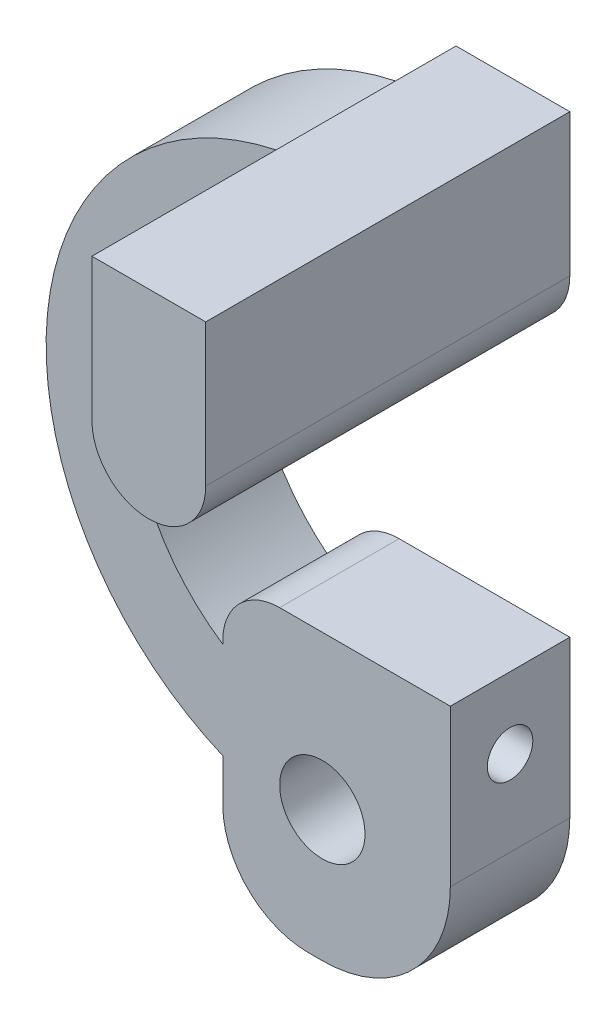
SolidWorks part; units mm, degrees
ref_plane "Front Plane" through (0, 0, 0) normal (0, 0, 1) x (1, 0, 0)
ref_plane "Top Plane" through (0, 0, 0) normal (0, 1, 0) x (1, 0, 0)
ref_plane "Right Plane" through (0, 0, 0) normal (1, 0, 0) x (0, 0, -1)
sketch "Sketch1" plane through (0, 0, 0) normal (0, 0, 1) x (1, 0, 0)
  line L0 (4, 24.097) -> (4, 3.674)
  line L1 (0, 0) -> (8, 0)
  line L2 (0, 0) -> (0, 26)
  line L3 (0, 26) -> (8, 26)
  line L4 (8, 0) -> (8, 26)
  line L5 (8, 26) -> (4, 26)
  line L6 (8, 26) -> (8, 19)
  line L7 (8, 19) -> (4, 19)
  line L8 (4, 26) -> (4, 19)
  line L9 (8, 0) -> (0, 0)
  line L10 (8, 0) -> (8, 10)
  line L11 (8, 10) -> (0, 10)
  line L12 (0, 0) -> (0, 10)
  circle A0 centre (4, 13.8855) radius 7.2115
  circle A1 centre (4, 13.8855) radius 10.2115
  dimension "D6" = 3
  dimension "D1" = 8
  dimension "D2" = 26
  dimension "D3" = 4
  dimension "D4" = 7
  dimension "D5" = 10
extrude "Boss-Extrude1" add sketch "Sketch1" along normal blind 4.2 contours A1 L4 L3 L8 | L6 A1 L0 A0 | L4 A0 L8 L7 | L0 A1 L2 A0 | L2 A1 L12 A0 | L12 A1 L0 A0 | A1 L2 L1 L4 | L0 A0 L10 L11 | L12 A0 L0 L11 | L0 A1 L10 A0 region at (6.0404, 22.2578, 0) region at (6.1243, 24.9013, 0) region at (1.9596, 22.2578, 0) region at (5.7682, 19.8911, 0) region at (-0.1979, 21.5835, 0) region at (4, 1.9782, 0) region at (1.9596, 5.5132, 0) region at (5.8652, 8.51, 0) region at (2.1348, 8.51, 0) region at (6.0404, 5.5132, 0)
sketch "Sketch2" plane through (0, 0, 4.2) normal (0, 0, 1) x (1, 0, 0)
  line L1 (4, 26) -> (8, 26)
  line L2 (4, 26) -> (4, 19)
  line L3 (4, 19) -> (8, 19)
  line L4 (8, 26) -> (8, 19)
extrude "Boss-Extrude2" add sketch "Sketch2" along normal blind 8.6
fillet "Fillet1" radius 4.5 1 edges at (8, 0, 2.1)
hole_wizard "Hole1" positions "3DSketch1" profile "Sketch3" legacy
sketch3d "3DSketch1"
  line L0 (8, 4.5, 4.2) -> (8, 10, 4.2) construction
  line L1 (0, 0, 4.2) -> (3.5, 0, 4.2) construction
  point P0 (3.5, 4.6, 4.2)
  dimension "D1" = 4.5
  dimension "D2" = 4.6
sketch "Sketch3" plane through (3.5, 4.6, 4.2) normal (1, 0, 0) x (0, -1, 0)
  line L0 (0, 0) -> (0, 100)
  line L1 (0, 100) -> (1.5, 100)
  line L2 (1.5, 100) -> (1.5, 0)
  line L3 (1.5, 0) -> (0, 0)
  line L4 (0, 110) -> (0, -10) construction
  dimension "Diameter" = 3
  dimension "Depth" = 100
fillet "Fillet3" radius 2 1 edges at (0, 10, 2.1)
fillet "Fillet4" radius 2 2 edges at (8, 19, 6.4) (4, 19, 6.4)
sketch "Sketch4" plane through (8, 0, 0) normal (1, 0, 0) x (0, 0, -1)
  line L0 (-12.8, 21) -> (-12.8, 26) construction
  line L1 (-12.8, 26) -> (0, 26) construction
  circle A0 centre (-10.1691, 23) radius 1.05
  circle A1 centre (-3.3691, 23) radius 1.05
  dimension "D4" = 2.1
  dimension "D5" = 2.1
  dimension "D6" = 3
  dimension "D1" = 2.6309
  dimension "D2" = 0
  dimension "D3" = 6.8
fillet "Fillet5" radius 3 1 edges at (0, 0, 2.1)
hole_wizard "Tap Drill for M2x0.4 Tap1" positions "3DSketch2" profile "Sketch6" hole size "M2x0.4" standard "ANSI Metric"
sketch3d "3DSketch2"
  line L0 (8, 10, 4.2) -> (8, 10, 0) construction
  line L1 (8, 4.5, 0) -> (8, 10, 0) construction
  point P0 (8, 7.5, 2.1)
  dimension "D1" = 2.5
  dimension "D2" = 2.1
sketch "Sketch6" plane through (8, 7.5, 2.1) normal (0, 1, 0) x (0, 0, -1)
  line L0 (0, 0) -> (0, 2.4607)
  line L1 (0, 2.4607) -> (0.8, 1.98)
  line L2 (0.8, 1.98) -> (0.8, 0)
  line L5 (0.8, 0) -> (0, 0)
  line L10 (0, 2.4607) -> (-0.8, 1.98) construction
  line L11 (0, -6.35) -> (0, 107.95) construction
  dimension "Hole Dia." = 1.6
  dimension "Hole Depth" = 1.98
  dimension "Drill Angle" = 118
